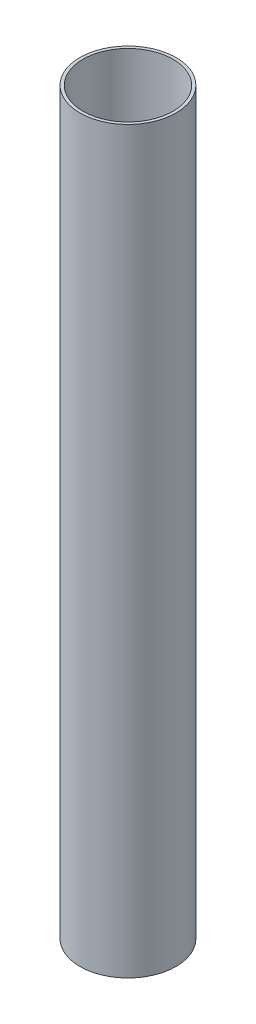
SolidWorks part; units mm, degrees
ref_plane "Front Plane" through (0, 0, 0) normal (0, 0, 1) x (1, 0, 0)
ref_plane "Top Plane" through (0, 0, 0) normal (0, 1, 0) x (1, 0, 0)
ref_plane "Right Plane" through (0, 0, 0) normal (1, 0, 0) x (0, 0, -1)
sketch "Sketch1" plane through (0, 0, 0) normal (0, 1, 0) x (1, 0, 0)
  circle A0 centre (0, 0) radius 32.5
  circle A1 centre (0, 0) radius 30.5
extrude "Boss-Extrude1" add sketch "Sketch1" along normal blind 500
